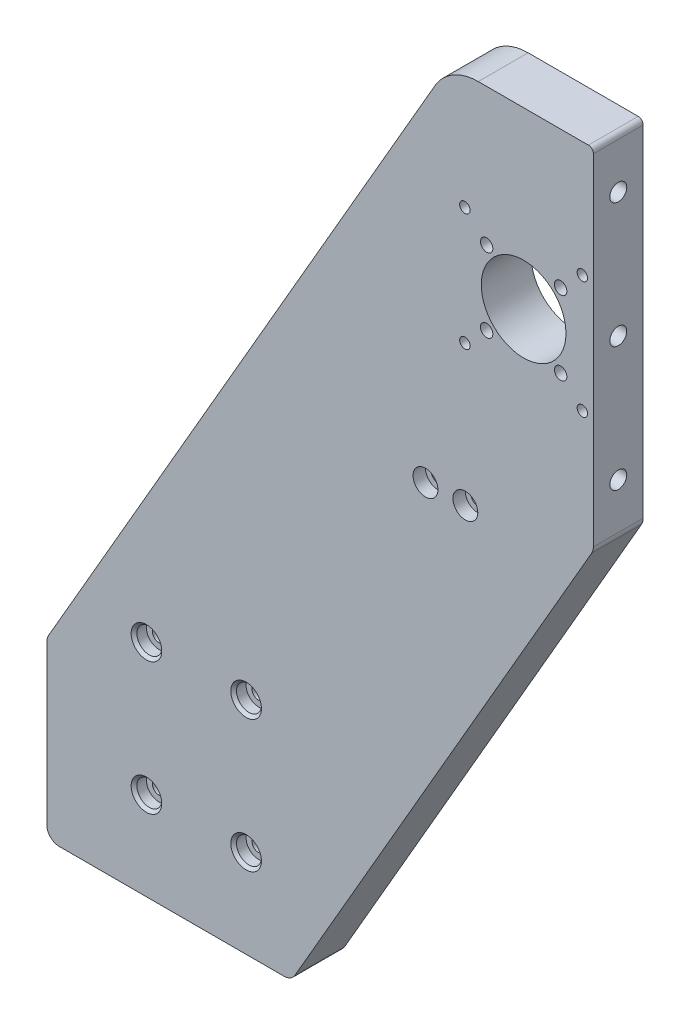
SolidWorks part; units mm, degrees
ref_plane "Piano frontale" through (0, 0, 0) normal (0, 0, 1) x (1, 0, 0)
ref_plane "Piano superiore" through (0, 0, 0) normal (0, 1, 0) x (1, 0, 0)
ref_plane "Piano destro" through (0, 0, 0) normal (1, 0, 0) x (0, 0, -1)
sketch "Schizzo1" plane through (0, 0, 0) normal (0, 0, 1) x (1, 0, 0)
  line L0 (5, 0) -> (95.2628, 0)
  line L1 (99.5929, 2.5) -> (218.7232, 208.8397)
  line L2 (219.3931, 211.3397) -> (219.3931, 348)
  line L3 (217.3931, 350) -> (173.2051, 350)
  line L4 (0, 68.6603) -> (0, 5)
  line L5 (155.8846, 340) -> (0.6699, 71.1603)
  line L6 (191.3931, 280) -> (191.3931, 350) construction
  line L9 (191.3931, 280) -> (176.5439, 294.8492) construction
  line L10 (191.3931, 280) -> (170.3931, 280) construction
  line L11 (191.3931, 280) -> (191.3931, 301) construction
  line L12 (50.1314, 0) -> (50.1314, 156.8301) construction
  circle A4 centre (191.3931, 280) radius 17
  circle A5 centre (191.3931, 280) radius 21 construction
  arc A6 (99.5929, 2.5) -> (95.2628, 0) centre (95.2628, 5) cw
  arc A7 (5, 0) -> (0, 5) centre (5, 5) cw
  arc A8 (0, 68.6603) -> (0.6699, 71.1603) centre (5, 68.6603) cw
  arc A9 (219.3931, 211.3397) -> (218.7232, 208.8397) centre (214.3931, 211.3397) cw
  arc A10 (219.3931, 348) -> (217.3931, 350) centre (217.3931, 348) ccw
  arc A11 (173.2051, 350) -> (155.8846, 340) centre (173.2051, 330) ccw
  circle A14 centre (206.2423, 294.8492) radius 2.5
  circle A15 centre (206.2423, 265.1508) radius 2.5
  circle A18 centre (176.5439, 265.1508) radius 2.5
  circle A19 centre (176.5439, 294.8492) radius 2.5
  point P27 (176.5439, 294.8492)
  point P28 (206.2423, 294.8492)
  point P29 (206.2423, 265.1508)
  point P30 (176.5439, 265.1508)
  point P31 (219.3931, 350)
  point P39 (0, 0)
  point P42 (0, 70)
  point P45 (219.3931, 210)
  point P48 (219.3931, 350)
  dimension "D6" = 70
  dimension "D9" = 34
  dimension "D11" = 45
  dimension "D14" = 5
  dimension "D15" = 5
  dimension "D17" = 42
  dimension "D12" = 2
  dimension "D1" = 120
  dimension "D2" = 120
  dimension "D3" = 70
  dimension "D4" = 350
  dimension "D5" = 140
  dimension "D10" = 28
extrude "Estrusione-Estrusione2" add sketch "Schizzo1" against normal blind 20
sketch "Sketch1" plane through (0, 0, 0) normal (0, -1, 0) x (1, 0, 0)
  line L0 (5, -10) -> (95.2628, -10) construction
  line L1 (5, -20) -> (5, 0) construction
  line L2 (95.2628, -20) -> (95.2628, 0) construction
  line L3 (50.1314, 0) -> (50.1314, -20) construction
  line L4 (5, 0) -> (95.2628, 0) construction
  line L5 (5, -20) -> (95.2628, -20) construction
  point P12 (50.1314, -10)
  point P13 (85.1314, -10)
  point P14 (15.1314, -10)
  dimension "D1" = 35
hole_wizard "M5 Tapped Hole1" positions "3DSketch1" profile "Sketch2" tap size "M5" standard "ISO"
sketch3d "3DSketch1"
  point P0 (50.1314, 0, -10)
  point P3 (85.1314, 0, -10)
  point P6 (15.1314, 0, -10)
sketch "Sketch2" plane through (50.1314, 0, -10) normal (1, 0, 0) x (0, 0, -1)
  line L0 (0, 0) -> (0, 18.6618)
  line L1 (0, 18.6618) -> (2.1, 17.4)
  line L2 (2.1, 17.4) -> (2.1, 0)
  line L5 (2.1, 0) -> (0, 0)
  line L10 (0, 18.6618) -> (-2.1, 17.4) construction
  line L11 (0, -6.35) -> (0, 107.95) construction
  dimension "Tap Drill Dia." = 4.2
  dimension "Tap Drill Depth" = 17.4
  dimension "Drill Angle" = 118
sketch "Sketch3" plane through (0, 0, 0) normal (0, 0, 1) x (1, 0, 0)
  line L0 (0, 68.6603) -> (0, 5) construction
  point P0 (40, 88.5)
  point P1 (80, 88.5)
  point P2 (80, 35.5)
  point P3 (40, 35.5)
  dimension "D1" = 40
  dimension "D2" = 53
  dimension "D3" = 40
hole_wizard "CBORE for M5 SHCS1" positions "3DSketch3" profile "Sketch5" counterbore size "M5" standard "ANSI Metric" end condition through all
sketch3d "3DSketch3"
  point P0 (80, 88.5, 0)
  point P3 (80, 35.5, 0)
  point P6 (40, 35.5, 0)
  point P9 (40, 88.5, 0)
sketch "Sketch5" plane through (80, 88.5, 0) normal (1, 0, 0) x (0, -1, 0)
  line L0 (0, 0) -> (0, 20)
  line L1 (0, 20) -> (2.65, 20)
  line L3 (2.65, 20) -> (2.65, 5)
  line L4 (5, 5) -> (2.65, 5)
  line L5 (5, 5) -> (5, 1.145)
  line L6 (5, 1.145) -> (6.145, 0)
  line L7 (6.145, 0) -> (0, 0)
  line L8 (-5, 1.145) -> (-6.145, 0) construction
  line L11 (0, -6.35) -> (0, 107.95) construction
  dimension "Thru Hole Dia." = 5.3
  dimension "Thru Hole Depth" = 20
  dimension "C'Bore Dia." = 10
  dimension "C'Bore Depth" = 5
  dimension "Near C'Sink Dia." = 12.29
  dimension "Near C'Sink Angle" = 90
sketch "Sketch7" plane through (219.3931, 0, 0) normal (1, 0, 0) x (0, 0, -1)
  line L0 (20, 279.6699) -> (0, 279.6699) construction
  line L1 (20, 211.3397) -> (20, 348) construction
  line L2 (0, 211.3397) -> (0, 348) construction
  point P0 (10, 329.6699)
  point P2 (10, 279.6699)
  point P4 (10, 229.6699)
  dimension "D1" = 50
  dimension "D2" = 50
hole_wizard "M8 Tapped Hole1" positions "3DSketch6" profile "Sketch12" tap size "M8" standard "ISO"
sketch3d "3DSketch6"
  point P0 (219.3931, 329.6699, -10)
  point P6 (219.3931, 279.6699, -10)
  point P12 (219.3931, 229.6699, -10)
sketch "Sketch12" plane through (219.3931, 329.6699, -10) normal (0, 1, 0) x (0, 0, -1)
  line L0 (0, 0) -> (0, 17.7929)
  line L1 (0, 17.7929) -> (3.4, 15.75)
  line L2 (3.4, 15.75) -> (3.4, 0)
  line L5 (3.4, 0) -> (0, 0)
  line L10 (0, 17.7929) -> (-3.4, 15.75) construction
  line L11 (0, -6.35) -> (0, 107.95) construction
  dimension "Tap Drill Dia." = 6.8
  dimension "Tap Drill Depth" = 15.75
  dimension "Drill Angle" = 118
sketch "Sketch24" plane through (0, 0, 0) normal (0, 0, 1) x (1, 0, 0)
  line L0 (191.3931, 280) -> (191.3931, 322.4149) construction
  line L1 (191.3931, 280) -> (226.3538, 280) construction
  point P3 (214.9631, 303.57)
  point P7 (167.8231, 303.57)
  point P8 (214.9631, 256.43)
  point P9 (167.8231, 256.43)
  dimension "D1" = 23.57
  dimension "D2" = 23.57
hole_wizard "M5 Tapped Hole2" positions "3DSketch9" profile "Sketch26" tap size "M5" standard "ISO" end condition through all
sketch3d "3DSketch9"
  point P0 (214.9631, 303.57, 0)
  point P3 (167.8231, 303.57, 0)
  point P6 (167.8231, 256.43, 0)
  point P9 (214.9631, 256.43, 0)
sketch "Sketch26" plane through (214.9631, 303.57, 0) normal (1, 0, 0) x (0, -1, 0)
  line L0 (0, 0) -> (0, 20)
  line L1 (0, 20) -> (2.1, 20)
  line L2 (2.1, 20) -> (2.1, 0)
  line L5 (2.1, 0) -> (0, 0)
  line L11 (0, -6.35) -> (0, 107.95) construction
  dimension "Thru Tap Drill Dia." = 4.2
  dimension "Thru Tap Drill Depth" = 20
cosmetic thread "Hole Thread1" parameters "D2"=5
cosmetic thread "Hole Thread2" parameters "D2"=5
cosmetic thread "Hole Thread3" parameters "D2"=5
cosmetic thread "Hole Thread4" parameters "D2"=5
sketch "Sketch27" plane through (0, 0, 0) normal (0, 0, 1) x (1, 0, 0)
  line L0 (146.5045, 200) -> (176.5045, 200) construction
  line L1 (168, 205) -> (168, 195) construction
  line L2 (5, 0) -> (95.2628, 0) construction
  line L3 (0, 68.6603) -> (0, 5) construction
  line L5 (160, 206.8242) -> (160, 192.8063) construction
  point P10 (168, 200)
  point P11 (152, 200)
  dimension "D1" = 200
  dimension "D2" = 160
  dimension "D3" = 8
hole_wizard "CBORE for M5 SHCS2" positions "3DSketch10" profile "Sketch28" counterbore size "M5" standard "ANSI Metric" end condition through all
sketch3d "3DSketch10"
  point P0 (152, 200, 0)
  point P3 (168, 200, 0)
sketch "Sketch28" plane through (152, 200, 0) normal (1, 0, 0) x (0, -1, 0)
  line L0 (0, 0) -> (0, 20)
  line L1 (0, 20) -> (2.65, 20)
  line L3 (2.65, 20) -> (2.65, 5)
  line L4 (2.65, 5) -> (5, 5)
  line L5 (5, 5) -> (5, 0)
  line L7 (5, 0) -> (0, 0)
  line L11 (0, -6.35) -> (0, 107.95) construction
  dimension "Thru Hole Dia." = 5.3
  dimension "Thru Hole Depth" = 20
  dimension "C'Bore Dia." = 10
  dimension "C'Bore Depth" = 5
